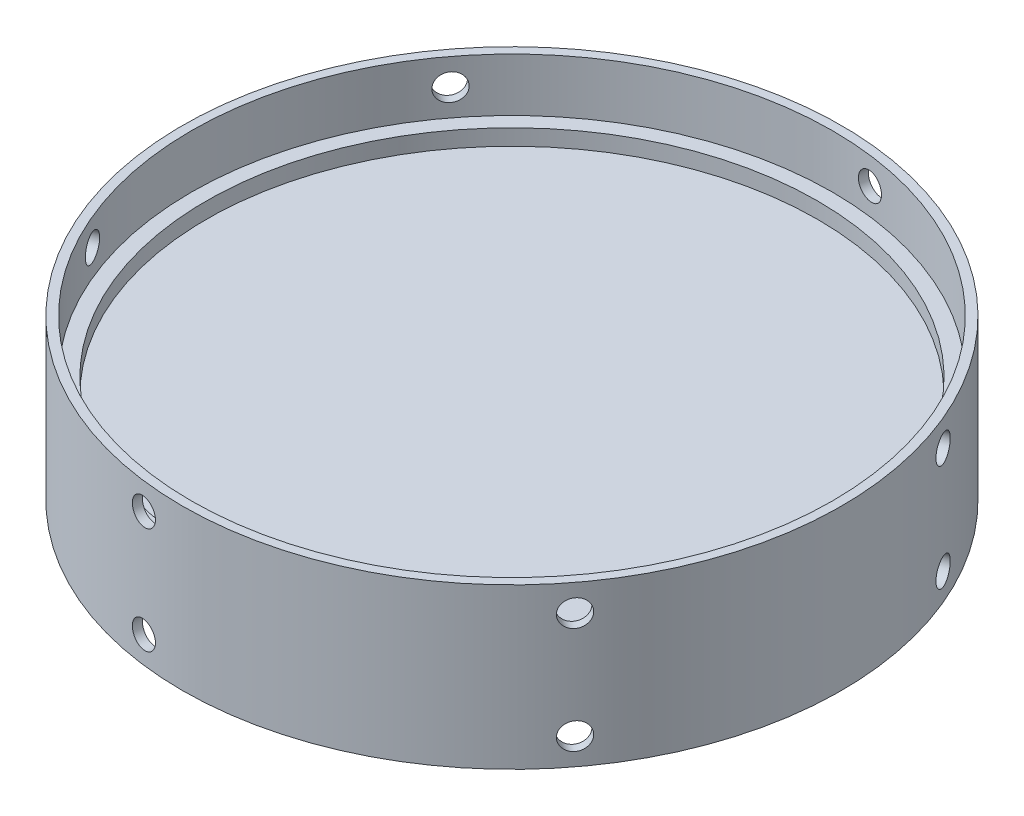
SolidWorks part; units mm, degrees
material "6061-T6 (SS)"
ref_plane "Front Plane" through (0, 0, 0) normal (0, 0, 1) x (1, 0, 0)
ref_plane "Top Plane" through (0, 0, 0) normal (0, 1, 0) x (1, 0, 0)
ref_plane "Right Plane" through (0, 0, 0) normal (1, 0, 0) x (0, 0, -1)
ref_axis "Axis1" through (0, 55, 0) along (0, -1, 0)
sketch "Sketch3" plane through (0, 0, 0) normal (0, 1, 0) x (1, 0, 0)
  circle A0 centre (0, 0) radius 78.5876
  dimension "D1" = 157.1752
extrude "Boss-Extrude1" add sketch "Sketch3" along normal blind 2.54 and the other way blind 2.54
sketch "Sketch4" plane through (0, 2.54, 0) normal (0, 1, 0) x (1, 0, 0)
  circle A0 centre (0, 0) radius 78.5876
  circle A1 centre (0, 0) radius 72.8662
  dimension "D1" = 157.1752
  dimension "D2" = 145.7325
extrude "Boss-Extrude3" add sketch "Sketch4" along normal blind 3.81
sketch "Sketch6" plane through (0, 6.35, 0) normal (0, 1, 0) x (1, 0, 0)
  circle A0 centre (0, 0) radius 78.5876
  circle A1 centre (0, 0) radius 76.454
  dimension "D1" = 157.1752
  dimension "D2" = 152.908
extrude "Boss-Extrude4" add sketch "Sketch6" along normal blind 12.7
hole_wizard "1/4 (0.25) Diameter Hole2" positions "3DSketch2" profile "Sketch7" hole size "1/4" standard "ANSI Inch" end condition up to next
sketch3d "3DSketch2"
  point P0 (-9.8633, 12.7, 77.9662)
  dimension "D1" = 6.35
sketch "Sketch7" plane through (-9.8633, 12.7, 77.9662) normal (0, 1, 0) x (0.9921, 0, 0.1255)
  line L0 (0, 0) -> (0, 185.7135)
  line L1 (0, 185.7135) -> (3.175, 185.7135)
  line L2 (3.175, 185.7135) -> (3.175, 0)
  line L5 (3.175, 0) -> (0, 0)
  line L11 (0, -6.35) -> (0, 107.95) construction
  dimension "Thru Hole Dia." = 6.35
  dimension "Thru Hole Depth" = 185.7135
pattern_circular "CirPattern2" count 6 over 360 about axis through (0, 55, 0) along (0, -1, 0) of "1/4 (0.25) Diameter Hole2"
mirror "Mirror3" about plane through (0, 0, 0) normal (0, 1, 0) of "Boss-Extrude3", "Boss-Extrude4", "1/4 (0.25) Diameter Hole2", "CirPattern2"
